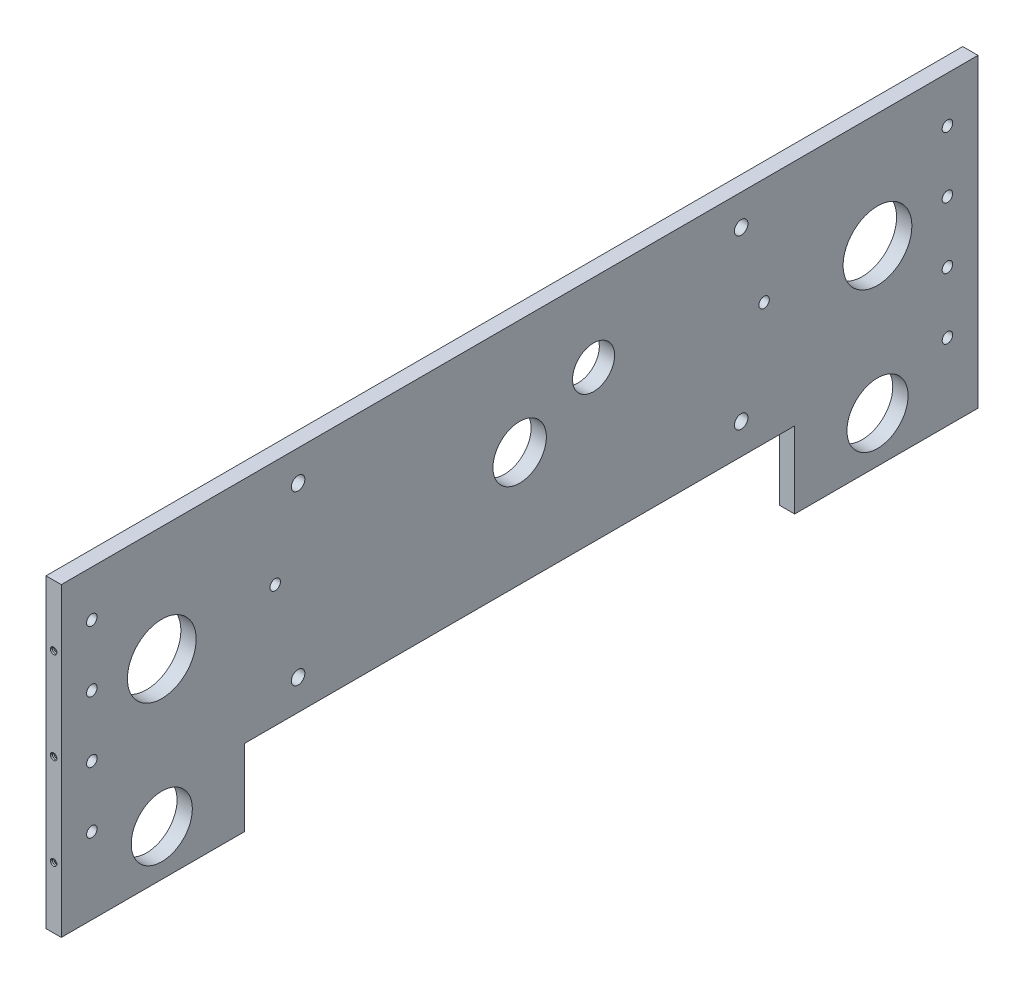
SolidWorks part; units mm, degrees
material "6061-T6 (SS)"
ref_plane "Front Plane" through (0, 0, 0) normal (0, 0, 1) x (1, 0, 0)
ref_plane "Top Plane" through (0, 0, 0) normal (0, 1, 0) x (1, 0, 0)
ref_plane "Right Plane" through (0, 0, 0) normal (1, 0, 0) x (0, 0, -1)
sketch "Sketch1" plane through (0, 0, 0) normal (1, 0, 0) x (0, 0, -1)
  line L1 (-190.5, 63.5) -> (190.5, 63.5)
  line L2 (-190.5, 63.5) -> (-190.5, -63.5)
  line L3 (-190.5, -63.5) -> (190.5, -63.5)
  line L4 (190.5, 63.5) -> (190.5, -63.5)
  line L5 (-190.5, 63.5) -> (190.5, -63.5) construction
  line L6 (-190.5, -63.5) -> (190.5, 63.5) construction
  point P0 (0, 0)
  dimension "D1" = 127
  dimension "D2" = 381
extrude "Boss-Extrude1" add sketch "Sketch1" along normal blind 6.35
sketch "Sketch2" plane through (6.35, 0, 0) normal (1, 0, 0) x (0, 0, -1)
  line L0 (-190.5, -63.5) -> (190.5, -63.5) construction
  line L1 (-148.7297, 15.875) -> (0, 15.875) construction
  line L2 (-74.3648, -34.925) -> (-74.3648, 15.875) construction
  line L3 (0, 15.875) -> (148.7297, 15.875) construction
  line L4 (74.3648, -34.925) -> (74.3648, 15.875) construction
  line L5 (190.5, 63.5) -> (-190.5, 63.5) construction
  line L6 (65.278, 53.34) -> (-56.642, 53.34) construction
  line L7 (65.278, 53.34) -> (65.278, -13.97) construction
  line L8 (65.278, -13.97) -> (-56.642, -13.97) construction
  line L9 (-56.642, 53.34) -> (-56.642, -13.97) construction
  line L10 (-190.5, -63.5) -> (190.5, -63.5) construction
  circle A1 centre (-148.7297, 15.875) radius 14.2875
  circle A2 centre (148.7297, 15.875) radius 14.2875
  circle A3 centre (-148.7297, 15.875) radius 38.1 construction
  circle A4 centre (0, 15.875) radius 38.1 construction
  circle A5 centre (148.7297, 15.875) radius 38.1 construction
  circle A6 centre (-74.3648, -34.925) radius 6.35 construction
  circle A7 centre (74.3648, -34.925) radius 6.35 construction
  circle A8 centre (-74.3648, 9.525) radius 6.35 construction
  circle A9 centre (74.3648, 9.525) radius 6.35 construction
  circle A11 centre (-148.7297, -44.4161) radius 12.7
  circle A12 centre (148.7297, -44.4161) radius 12.7
  circle A13 centre (0, 15.875) radius 29.2138 construction
  circle A14 centre (30.7215, 31.115) radius 5.08 construction
  circle A15 centre (30.7215, 31.115) radius 8.75
  circle A16 centre (0, 15.875) radius 11.1125
  point P11 (0, 0)
  dimension "D1" = 28.575
  dimension "D5" = 76.2
  dimension "D7" = 12.7
  dimension "D14" = 25.4
  dimension "D15" = 19.0839
  dimension "D17" = 25.4
  dimension "D20" = 58.4276
  dimension "D21" = 10.16
  dimension "D22" = 17.5001
  dimension "D24" = 22.225
  dimension "D25" = 28.575
  dimension "D26" = 22.225
  dimension "D2" = 79.375
  dimension "D3" = 148.7297
  dimension "D4" = 148.7297
  dimension "D6" = 0
  dimension "D8" = 28.575
  dimension "D9" = 44.45
  dimension "D10" = 56.642
  dimension "D11" = 121.92
  dimension "D12" = 10.16
  dimension "D13" = 49.53
  dimension "D16" = 148.7297
  dimension "D18" = 19.0839
  dimension "D19" = 148.7297
  dimension "D23" = 15.24
extrude "Cut-Extrude1" cut sketch "Sketch2" against normal through all
sketch "Sketch3" plane through (6.35, 0, 0) normal (1, 0, 0) x (0, 0, -1)
  line L0 (-184.404, 19.05) -> (-184.404, -19.05) construction
  line L1 (-190.5, 63.5) -> (-190.5, -63.5) construction
  point P2 (-184.404, 0)
  point P3 (-190.5, 0)
  dimension "D1" = 38.1
  dimension "D2" = 6.096
sketch "Sketch23" plane through (6.35, 0, 0) normal (1, 0, 0) x (0, 0, -1)
  line L0 (-114.3, -63.5) -> (-114.3, -31.75)
  line L1 (-190.5, -63.5) -> (190.5, -63.5) construction
  line L2 (-114.3, -31.75) -> (114.3, -31.75)
  line L3 (114.3, -31.75) -> (114.3, -63.5)
  line L4 (-190.5, 63.5) -> (-190.5, -63.5) construction
  line L5 (190.5, -63.5) -> (190.5, 63.5) construction
  line L6 (-114.3, -63.5) -> (114.3, -63.5)
  dimension "D1" = 31.75
  dimension "D2" = 76.2
  dimension "D3" = 76.2
extrude "Cut-Extrude6" cut sketch "Sketch23" against normal through all
sketch "Sketch24" plane through (0, 0, 0) normal (-1, 0, 0) x (0, 0, 1)
  line L0 (-190.5, -63.5) -> (-190.5, 63.5) construction
  line L1 (-190.5, 63.5) -> (190.5, 63.5) construction
  point P0 (-92.075, -19.05)
  point P1 (-92.075, 50.8)
  point P2 (92.075, -19.05)
  point P4 (92.075, 50.8)
  dimension "D1" = 69.85
  dimension "D2" = 98.425
  dimension "D3" = 12.7
  dimension "D4" = 12.7
  dimension "D5" = 69.85
  dimension "D6" = 184.15
hole_wizard "CSK for #10 Flat Head Machine Screw2" positions "Sketch25" profile "Sketch26" countersink size "#10" standard "ANSI Inch" end condition through all
sketch "Sketch25" plane through (0, 0, 0) normal (-1, 0, 0) x (0, 0, 1)
  point P0 (-92.075, 50.8)
  point P3 (-92.075, -19.05)
  point P6 (92.075, -19.05)
  point P9 (92.075, 50.8)
sketch "Sketch26" plane through (0, 50.8, -92.075) normal (0, 1, 0) x (0, 0, 1)
  line L0 (0, 0) -> (0, 6.35)
  line L1 (0, 6.35) -> (2.8067, 6.35)
  line L2 (2.8067, 6.35) -> (2.8067, 2.396)
  line L3 (2.8067, 2.396) -> (4.8895, 0)
  line L5 (4.8895, 0) -> (0, 0)
  line L6 (-2.8067, 2.396) -> (-4.8895, 0) construction
  line L11 (0, -6.35) -> (0, 107.95) construction
  dimension "Thru Hole Dia." = 5.6134
  dimension "Thru Hole Depth" = 6.35
  dimension "Near C'Sink Dia." = 9.779
  dimension "Near C'Sink Angle" = 82
sketch "Sketch27" plane through (6.35, 0, 0) normal (1, 0, 0) x (0, 0, -1)
  line L0 (190.5, -63.5) -> (190.5, 63.5) construction
  line L1 (114.3, -63.5) -> (190.5, -63.5) construction
  line L2 (-190.5, -63.5) -> (-114.3, -63.5) construction
  line L3 (-190.5, 63.5) -> (-190.5, -63.5) construction
  point P0 (177.8, -57.15)
  point P1 (177.8, -31.75)
  point P2 (177.8, -6.35)
  point P3 (177.8, 19.05)
  point P4 (177.8, 44.45)
  point P7 (-177.8, -57.15)
  point P8 (-177.8, -31.75)
  point P9 (-177.8, -6.35)
  point P10 (-177.8, 19.05)
  point P11 (-177.8, 44.45)
  dimension "D1" = 25.4
  dimension "D2" = 25.4
  dimension "D3" = 25.4
  dimension "D4" = 25.4
  dimension "D5" = 12.7
  dimension "D6" = 25.4
  dimension "D7" = 25.4
  dimension "D8" = 25.4
  dimension "D9" = 25.4
  dimension "D10" = 6.35
  dimension "D11" = 6.35
  dimension "D12" = 12.7
hole_wizard "11/64 (0.17188) Diameter Hole1" positions "Sketch28" profile "Sketch29" hole size "11/64" standard "ANSI Inch" end condition through all
sketch "Sketch28" plane through (6.35, 0, 0) normal (1, 0, 0) x (0, 0, -1)
  point P0 (-177.8, 44.45)
  point P3 (-177.8, 19.05)
  point P6 (-177.8, -6.35)
  point P9 (-177.8, -31.75)
  point P12 (177.8, -31.75)
  point P15 (177.8, -6.35)
  point P18 (177.8, 19.05)
  point P21 (177.8, 44.45)
sketch "Sketch29" plane through (6.35, 44.45, 177.8) normal (0, 1, 0) x (0, 0, -1)
  line L0 (0, 0) -> (0, 6.35)
  line L1 (0, 6.35) -> (2.1829, 6.35)
  line L2 (2.1829, 6.35) -> (2.1829, 0)
  line L5 (2.1829, 0) -> (0, 0)
  line L11 (0, -6.35) -> (0, 107.95) construction
  dimension "Thru Hole Dia." = 4.3658
  dimension "Thru Hole Depth" = 6.35
sketch "Sketch30" plane through (6.35, 0, 0) normal (1, 0, 0) x (0, 0, -1)
  line L0 (-190.5, 63.5) -> (-190.5, -63.5) construction
  line L1 (190.5, -63.5) -> (190.5, 63.5) construction
  line L2 (190.5, 63.5) -> (-190.5, 63.5) construction
  point P0 (-101.6, 19.05)
  point P1 (101.6, 19.05)
  dimension "D1" = 88.9
  dimension "D2" = 88.9
  dimension "D3" = 44.45
hole_wizard "11/64 (0.17188) Diameter Hole2" positions "Sketch31" profile "Sketch32" hole size "11/64" standard "ANSI Inch"
sketch "Sketch31" plane through (6.35, 0, 0) normal (1, 0, 0) x (0, 0, -1)
  point P0 (-101.6, 19.05)
  point P3 (101.6, 19.05)
sketch "Sketch32" plane through (6.35, 19.05, 101.6) normal (0, 1, 0) x (0, 0, -1)
  line L0 (0, 0) -> (0, 10.2016)
  line L1 (0, 10.2016) -> (2.1829, 8.89)
  line L2 (2.1829, 8.89) -> (2.1829, 0)
  line L5 (2.1829, 0) -> (0, 0)
  line L10 (0, 10.2016) -> (-2.1829, 8.89) construction
  line L11 (0, -6.35) -> (0, 107.95) construction
  dimension "Hole Dia." = 4.3658
  dimension "Hole Depth" = 8.89
  dimension "Drill Angle" = 118
sketch "Sketch33" plane through (0, 0, 190.5) normal (0, 0, 1) x (1, 0, 0)
  line L0 (6.35, 63.5) -> (0, 63.5) construction
  line L1 (0, 63.5) -> (0, -63.5) construction
  point P0 (3.175, 38.1)
  point P1 (3.175, 0)
  point P2 (3.175, -38.1)
  dimension "D1" = 25.4
  dimension "D2" = 3.175
  dimension "D3" = 38.1
  dimension "D4" = 38.1
hole_wizard "#36 (0.1065) Diameter Hole1" positions "Sketch34" profile "Sketch35" hole size "#36" standard "ANSI Inch"
sketch "Sketch34" plane through (0, 0, 190.5) normal (0, 0, 1) x (1, 0, 0)
  point P0 (3.175, 38.1)
  point P3 (3.175, -38.1)
  point P6 (3.175, 0)
sketch "Sketch35" plane through (3.175, 38.1, 190.5) normal (1, 0, 0) x (0, -1, 0)
  line L0 (0, 0) -> (0, 9.7027)
  line L1 (0, 9.7027) -> (1.3525, 8.89)
  line L2 (1.3525, 8.89) -> (1.3525, 0)
  line L5 (1.3525, 0) -> (0, 0)
  line L10 (0, 9.7027) -> (-1.3525, 8.89) construction
  line L11 (0, -6.35) -> (0, 107.95) construction
  dimension "Hole Dia." = 2.7051
  dimension "Hole Depth" = 8.89
  dimension "Drill Angle" = 118
thread "Thread1" pitch 0.7937 method cut profile "Thread Profile1" start angle 0, offset 0, length 6.35, pitch 0.7937, diameter 2.7051
ref_plane "Plane1" through (1.8225, 38.1, 190.5) normal (0, -1, 0) x (-1, 0, 0)
sketch "Thread Profile1" plane through (1.8225, 38.1, 190.5) normal (0, -1, 0) x (-1, 0, 0)
  line L0 (0, 0) -> (0, 0.7937) construction
  line L1 (0, 0) -> (0.4296, 0.248)
  line L2 (0.4296, 0.248) -> (0.4296, 0.3473)
  line L3 (0.4296, 0.3473) -> (0, 0.5953)
  line L4 (0.4296, 0.2977) -> (0, 0.2977) construction
  line L11 (0, 0) -> (0, 0.5953)
  point P2 (0, 0)
  dimension "Pitch" = 0.7937
  dimension "Profile_Angle" = 60
  dimension "Profile_Land" = 0.0992
  dimension "Profile_Height" = 0.4296
thread "Thread2" pitch 0.7937 method cut profile "Thread Profile2" start angle 0, offset 0, length 6.35, pitch 0.7937, diameter 2.7051
ref_plane "Plane2" through (1.8225, 0, 190.5) normal (0, -1, 0) x (-1, 0, 0)
sketch "Thread Profile2" plane through (1.8225, 0, 190.5) normal (0, -1, 0) x (-1, 0, 0)
  line L0 (0, 0) -> (0, 0.7937) construction
  line L1 (0, 0) -> (0.4296, 0.248)
  line L2 (0.4296, 0.248) -> (0.4296, 0.3473)
  line L3 (0.4296, 0.3473) -> (0, 0.5953)
  line L4 (0.4296, 0.2977) -> (0, 0.2977) construction
  line L11 (0, 0) -> (0, 0.5953)
  point P2 (0, 0)
  dimension "Pitch" = 0.7937
  dimension "Profile_Angle" = 60
  dimension "Profile_Land" = 0.0992
  dimension "Profile_Height" = 0.4296
thread "Thread3" pitch 0.7937 method cut profile "Thread Profile3" start angle 0, offset 0, length 6.35, pitch 0.7937, diameter 2.7051
ref_plane "Plane3" through (1.8225, -38.1, 190.5) normal (0, -1, 0) x (-1, 0, 0)
sketch "Thread Profile3" plane through (1.8225, -38.1, 190.5) normal (0, -1, 0) x (-1, 0, 0)
  line L0 (0, 0) -> (0, 0.7937) construction
  line L1 (0, 0) -> (0.4296, 0.248)
  line L2 (0.4296, 0.248) -> (0.4296, 0.3473)
  line L3 (0.4296, 0.3473) -> (0, 0.5953)
  line L4 (0.4296, 0.2977) -> (0, 0.2977) construction
  line L11 (0, 0) -> (0, 0.5953)
  point P2 (0, 0)
  dimension "Pitch" = 0.7937
  dimension "Profile_Angle" = 60
  dimension "Profile_Land" = 0.0992
  dimension "Profile_Height" = 0.4296
sketch "Sketch42" plane through (0, 0, -190.5) normal (0, 0, -1) x (-1, 0, 0)
  line L0 (-6.35, 63.5) -> (0, 63.5) construction
  line L2 (-6.35, -63.5) -> (-6.35, 63.5) construction
  point P0 (-3.175, 38.1)
  point P1 (-3.175, 0)
  point P2 (-3.175, -38.1)
  dimension "D1" = 25.4
  dimension "D2" = 3.175
hole_wizard "#36 (0.1065) Diameter Hole2" positions "Sketch43" profile "Sketch44" hole size "#36" standard "ANSI Inch"
sketch "Sketch43" plane through (0, 0, -190.5) normal (0, 0, -1) x (-1, 0, 0)
  point P0 (-3.175, 38.1)
  point P3 (-3.175, 0)
  point P6 (-3.175, -38.1)
sketch "Sketch44" plane through (3.175, 38.1, -190.5) normal (1, 0, 0) x (0, 1, 0)
  line L0 (0, 0) -> (0, 9.7027)
  line L1 (0, 9.7027) -> (1.3525, 8.89)
  line L2 (1.3525, 8.89) -> (1.3525, 0)
  line L5 (1.3525, 0) -> (0, 0)
  line L10 (0, 9.7027) -> (-1.3525, 8.89) construction
  line L11 (0, -6.35) -> (0, 107.95) construction
  dimension "Hole Dia." = 2.7051
  dimension "Hole Depth" = 8.89
  dimension "Drill Angle" = 118
thread "Thread4" pitch 0.7937 method cut profile "Thread Profile4" start angle 0, offset 0, length 6.35, pitch 0.7937, diameter 2.7051
ref_plane "Plane4" through (4.5275, 38.1, -190.5) normal (0, -1, 0) x (1, 0, 0)
sketch "Thread Profile4" plane through (4.5275, 38.1, -190.5) normal (0, -1, 0) x (1, 0, 0)
  line L0 (0, 0) -> (0, 0.7937) construction
  line L1 (0, 0) -> (0.4296, 0.248)
  line L2 (0.4296, 0.248) -> (0.4296, 0.3473)
  line L3 (0.4296, 0.3473) -> (0, 0.5953)
  line L4 (0.4296, 0.2977) -> (0, 0.2977) construction
  line L11 (0, 0) -> (0, 0.5953)
  point P2 (0, 0)
  dimension "Pitch" = 0.7937
  dimension "Profile_Angle" = 60
  dimension "Profile_Land" = 0.0992
  dimension "Profile_Height" = 0.4296
thread "Thread5" pitch 0.7937 method cut profile "Thread Profile5" start angle 0, offset 0, length 6.35, pitch 0.7937, diameter 2.7051
ref_plane "Plane5" through (4.5275, 0, -190.5) normal (0, -1, 0) x (1, 0, 0)
sketch "Thread Profile5" plane through (4.5275, 0, -190.5) normal (0, -1, 0) x (1, 0, 0)
  line L0 (0, 0) -> (0, 0.7937) construction
  line L1 (0, 0) -> (0.4296, 0.248)
  line L2 (0.4296, 0.248) -> (0.4296, 0.3473)
  line L3 (0.4296, 0.3473) -> (0, 0.5953)
  line L4 (0.4296, 0.2977) -> (0, 0.2977) construction
  line L11 (0, 0) -> (0, 0.5953)
  point P2 (0, 0)
  dimension "Pitch" = 0.7937
  dimension "Profile_Angle" = 60
  dimension "Profile_Land" = 0.0992
  dimension "Profile_Height" = 0.4296
thread "Thread6" pitch 0.7937 method cut profile "Thread Profile6" start angle 0, offset 0, length 6.35, pitch 0.7937, diameter 2.7051
ref_plane "Plane6" through (4.5275, -38.1, -190.5) normal (0, -1, 0) x (1, 0, 0)
sketch "Thread Profile6" plane through (4.5275, -38.1, -190.5) normal (0, -1, 0) x (1, 0, 0)
  line L0 (0, 0) -> (0, 0.7937) construction
  line L1 (0, 0) -> (0.4296, 0.248)
  line L2 (0.4296, 0.248) -> (0.4296, 0.3473)
  line L3 (0.4296, 0.3473) -> (0, 0.5953)
  line L4 (0.4296, 0.2977) -> (0, 0.2977) construction
  line L11 (0, 0) -> (0, 0.5953)
  point P2 (0, 0)
  dimension "Pitch" = 0.7937
  dimension "Profile_Angle" = 60
  dimension "Profile_Land" = 0.0992
  dimension "Profile_Height" = 0.4296
